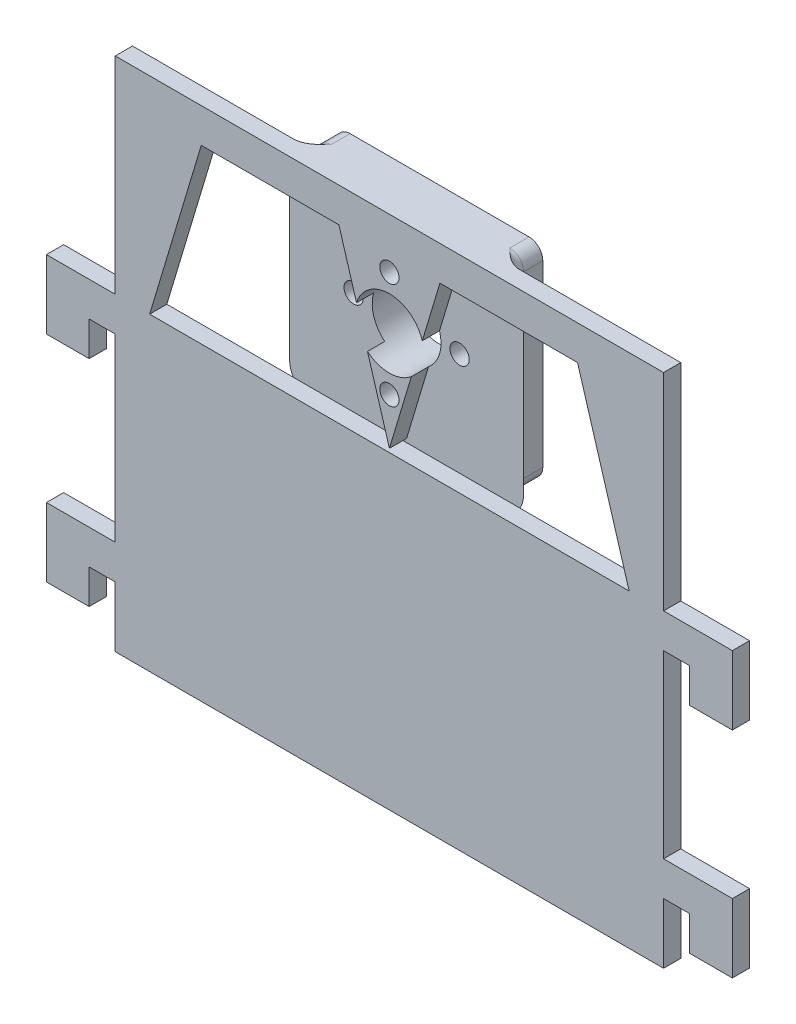
SolidWorks part; units mm, degrees
ref_plane "Front" through (0, 0, 0) normal (0, 0, 1) x (1, 0, 0)
ref_plane "Top" through (0, 0, 0) normal (0, 1, 0) x (1, 0, 0)
ref_plane "Right" through (0, 0, 0) normal (1, 0, 0) x (0, 0, -1)
sketch "Sketch1" plane through (0, 0, 0) normal (0, 0, 1) x (1, 0, 0)
  line L1 (0, 0) -> (-38.1, 0)
  line L2 (0, 0) -> (0, -38.1)
  line L3 (0, -38.1) -> (-38.1, -38.1)
  line L4 (-38.1, 0) -> (-38.1, -38.1)
  dimension "D1" = 38.1
  dimension "D2" = 38.1
extrude "Boss-Extrude1" add sketch "Sketch1" along normal blind 9.2583
sketch "Sketch2" plane through (0, 0, 9.2583) normal (0, 0, 1) x (1, 0, 0)
  line L0 (0, 0) -> (-38.1, 0) construction
  line L1 (0, -38.1) -> (0, 0) construction
  circle A0 centre (-19.05, -19.05) radius 6.35
  dimension "D1" = 12.7
  dimension "D2" = 19.05
  dimension "D3" = 19.05
extrude "Cut-Extrude1" cut sketch "Sketch2" against normal blind 10.8458
sketch "Sketch3" plane through (0, 0, 9.2583) normal (0, 0, 1) x (1, 0, 0)
  circle A0 centre (-19.05, -9.271) radius 1.778
  circle A1 centre (-19.05, -19.05) radius 6.35 construction
  dimension "D1" = 3.556
  dimension "D2" = 9.779
extrude "Cut-Extrude2" cut sketch "Sketch3" against normal blind 10.8458
pattern_circular "CirPattern1" count 4 over 360 about axis through (-19.05, -19.05, 9.2583) along (0, 0, 1) of "Cut-Extrude2"
sketch "Sketch4" plane through (0, 0, 9.2583) normal (0, 0, 1) x (1, 0, 0)
  line L1 (-38.1, 0) -> (-69.6468, 0)
  line L2 (-38.1, 0) -> (-38.1, -95.2246)
  line L3 (-38.1, -95.2246) -> (-69.6468, -95.2246)
  line L4 (-69.6468, 0) -> (-69.6468, -95.2246)
  line L5 (0, 0) -> (31.5468, 0)
  line L6 (0, 0) -> (0, -95.2246)
  line L7 (0, -95.2246) -> (31.5468, -95.2246)
  line L8 (31.5468, 0) -> (31.5468, -95.2246)
  dimension "D1" = 31.5468
  dimension "D2" = 31.5468
  dimension "D3" = 95.2246
  dimension "D4" = 95.2246
extrude "Boss-Extrude2" add sketch "Sketch4" against normal blind 3.175
sketch "Sketch5" plane through (0, 0, 6.0833) normal (0, 0, -1) x (-1, 0, 0)
  line L1 (0, -38.1) -> (38.1, -38.1)
  line L2 (0, -38.1) -> (0, -95.2246)
  line L3 (0, -95.2246) -> (38.1, -95.2246)
  line L4 (38.1, -38.1) -> (38.1, -95.2246)
extrude "Boss-Extrude3" add sketch "Sketch5" against normal blind 3.175
fillet "Fillet1" radius 2.54 4 edges at (-38.1, 0, 3.0416) (-38.1, -38.1, 3.0416) (0, -38.1, 3.0416) (0, 0, 3.0416)
fillet "Fillet2" radius 2.54 7 edges at (-0.7439, -0.7439, 6.0833) (-37.3561, -0.7439, 6.0833) (-38.1, -19.05, 6.0833) (-37.3561, -37.3561, 6.0833) (-19.05, -38.1, 6.0833) (-0.7439, -37.3561, 6.0833) (0, -19.05, 6.0833)
sketch "Sketch6" plane through (0, 0, 6.0833) normal (0, 0, -1) x (-1, 0, 0)
  line L0 (-31.5468, -95.2246) -> (-31.5468, 0) construction
  line L3 (-36.3728, -50.8) -> (-44.2468, -50.8)
  line L5 (-44.2468, -38.1) -> (-44.2468, -50.8)
  line L8 (-44.2468, -38.1) -> (-31.5468, -38.1)
  line L9 (-31.5468, -44.45) -> (-31.5468, -38.1)
  line L14 (-36.3728, -90.424) -> (-44.2468, -90.424)
  line L17 (-31.5468, -44.45) -> (-36.3728, -44.45)
  line L18 (-36.3728, -50.8) -> (-36.3728, -44.45)
  line L19 (-44.2468, -77.724) -> (-44.2468, -90.424)
  line L20 (-44.2468, -77.724) -> (-31.5468, -77.724)
  line L21 (-31.5468, -84.074) -> (-31.5468, -77.724)
  line L22 (-31.5468, -84.074) -> (-36.3728, -84.074)
  line L23 (-36.3728, -90.424) -> (-36.3728, -84.074)
  line L24 (-31.5468, -95.2246) -> (-31.5468, 0) construction
  line L25 (-31.5468, 0) -> (-1.8594, 0) construction
  dimension "D1" = 12.7
  dimension "D2" = 12.7
  dimension "D3" = 26.924
  dimension "D4" = 6.35
  dimension "D5" = 38.1
  dimension "D6" = 4.826
  dimension "D7" = 6.35
  dimension "D8" = 12.7
  dimension "D9" = 4.826
  dimension "D10" = 12.7
extrude "Boss-Extrude4" add sketch "Sketch6" against normal blind 3.175
ref_plane "Plane1" through (-19.05, 0, 0) normal (1, 0, 0) x (0, 0, -1)
mirror "Mirror2" about plane through (-19.05, 0, 0) normal (1, 0, 0) of "Boss-Extrude4"
sketch "Sketch8" plane through (0, 0, 6.0833) normal (0, 0, -1) x (-1, 0, 0)
  line L0 (-25.1968, -38.1) -> (19.2532, -38.1)
  line L1 (19.2532, -38.1) -> (9.7282, -6.35)
  line L2 (9.7282, -6.35) -> (-15.6718, -6.35)
  line L3 (-15.6718, -6.35) -> (-25.1968, -38.1)
  line L5 (-31.5468, 0) -> (-1.8594, 0) construction
  line L6 (-31.5468, -77.724) -> (-31.5468, -44.45) construction
  dimension "D1" = 44.45
  dimension "D2" = 6.35
  dimension "D3" = 6.35
  dimension "D4" = 31.75
  dimension "D5" = 25.4
  dimension "D6" = 9.525
extrude "Cut-Extrude3" cut sketch "Sketch8" against normal blind 4.7625
mirror "Mirror3" about plane through (-19.05, 0, 0) normal (1, 0, 0) of "Cut-Extrude3"
ref_plane "Plane2" through (0, -67.2846, 0) normal (0, -1, 0) x (-1, 0, 0)
